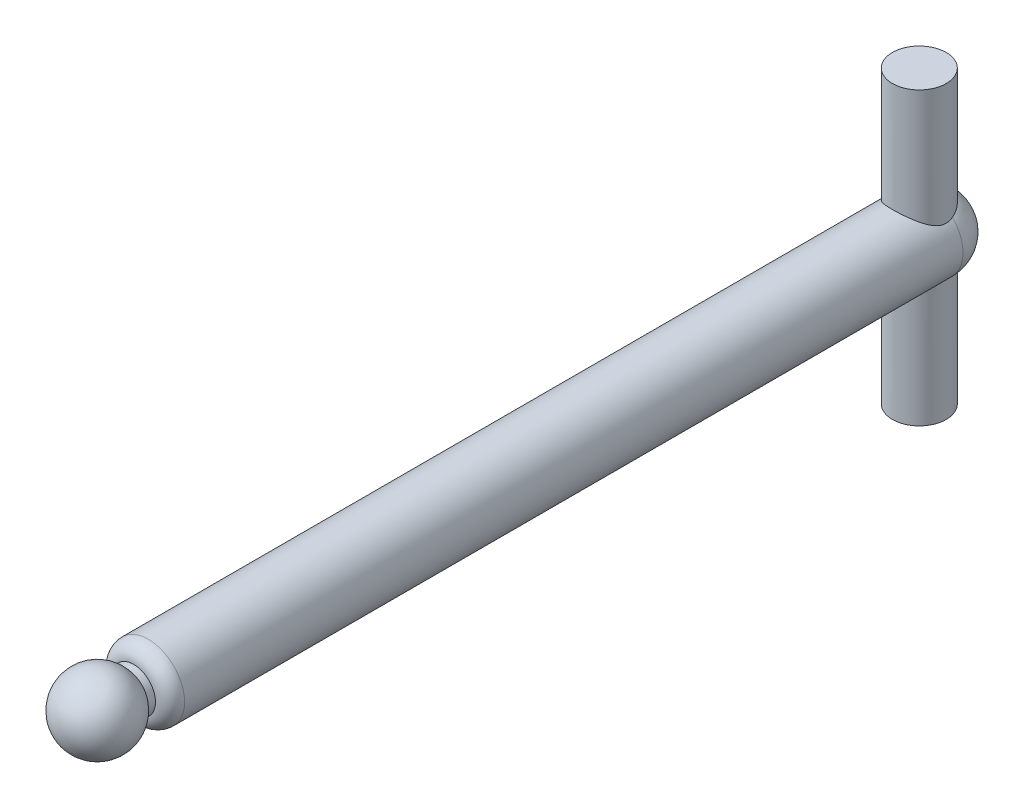
SolidWorks part; units mm, degrees
ref_plane "Front Plane" through (0, 0, 0) normal (0, 0, 1) x (1, 0, 0)
ref_plane "Top Plane" through (0, 0, 0) normal (0, 1, 0) x (1, 0, 0)
ref_plane "Right Plane" through (0, 0, 0) normal (1, 0, 0) x (0, 0, -1)
sketch "Sketch1" plane through (0, 0, 0) normal (0, 0, 1) x (1, 0, 0)
  circle A0 centre (0, 0) radius 2.5
  dimension "D1" = 5
extrude "Boss-Extrude1" add sketch "Sketch1" along normal blind 57
sketch "Sketch2" plane through (0, 0, 0) normal (0, 1, 0) x (1, 0, 0)
  line L0 (-2.5, -57) -> (2.5, -57)
sketch "Sketch3" plane through (0, 0, 0) normal (0, 1, 0) x (1, 0, 0)
  line L0 (-2.5, -57) -> (2.5, -57) construction
  line L1 (0, -57) -> (0, -62)
  line L3 (0, -29.8406) -> (-1.5, -29.8406)
  line L4 (0, -29.8406) -> (0, -27.9123)
  line L5 (0, -27.9123) -> (-1.5, -27.9123)
  line L6 (-1.5, -29.8406) -> (-1.5, -27.9123)
  line L7 (0, -58.3764) -> (-1.5, -58.3764)
  line L8 (0, -58.3764) -> (0, -54.7491)
  line L9 (0, -54.7491) -> (-1.5, -54.7491)
  line L10 (-1.5, -58.3764) -> (-1.5, -54.7491)
  arc A1 (0, -57) -> (0, -62) centre (0, -59.5) ccw
  dimension "D1" = 1.5
  dimension "D2" = 2.5
revolve "Revolve1" add sketch "Sketch3" angle 360 about L1
fillet "Fillet1" radius 1 1 edges at (2.5, 0, 57)
sketch "Sketch4" plane through (0, 0, 0) normal (0, 1, 0) x (1, 0, 0)
  circle A0 centre (0, -3) radius 1.85
  dimension "D1" = 3.7
  dimension "D2" = 3
extrude "Boss-Extrude2" add sketch "Sketch4" along normal blind 10 and the other way blind 10 contours A0
fillet "Fillet2" radius 2.5 1 edges at (2.5, 0, 0)
